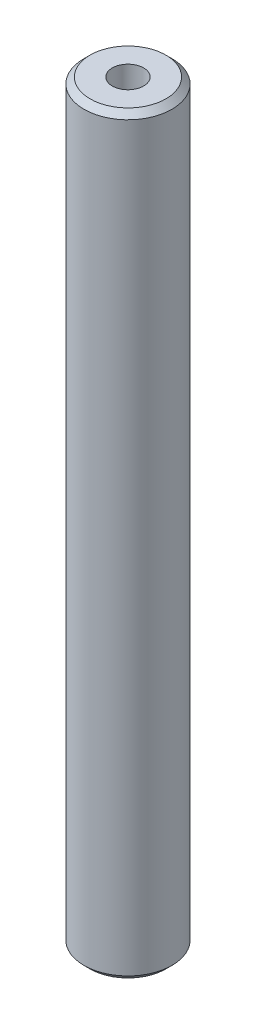
SolidWorks part; units mm, degrees
ref_plane "Front Plane" through (0, 0, 0) normal (0, 0, 1) x (1, 0, 0)
ref_plane "Top Plane" through (0, 0, 0) normal (0, 1, 0) x (1, 0, 0)
ref_plane "Right Plane" through (0, 0, 0) normal (1, 0, 0) x (0, 0, -1)
sketch "Sketch1" plane through (0, 0, 0) normal (0, 1, 0) x (1, 0, 0)
  circle A0 centre (0, 0) radius 35
  dimension "SHAFT_OD" = 70
extrude "Boss-Extrude1" add sketch "Sketch1" along normal blind 600
sketch "Sketch2" plane through (0, 0, 0) normal (0, 1, 0) x (1, 0, 0)
  circle A0 centre (0, 0) radius 12.5021
  dimension "BORE_D" = 25.0041
extrude "Cut-Extrude1" cut sketch "Sketch2" along normal through all
chamfer "Chamfer1" distance 4.7977 angle 45 2 edges at (0, 600, 35) (0, 0, 35)
